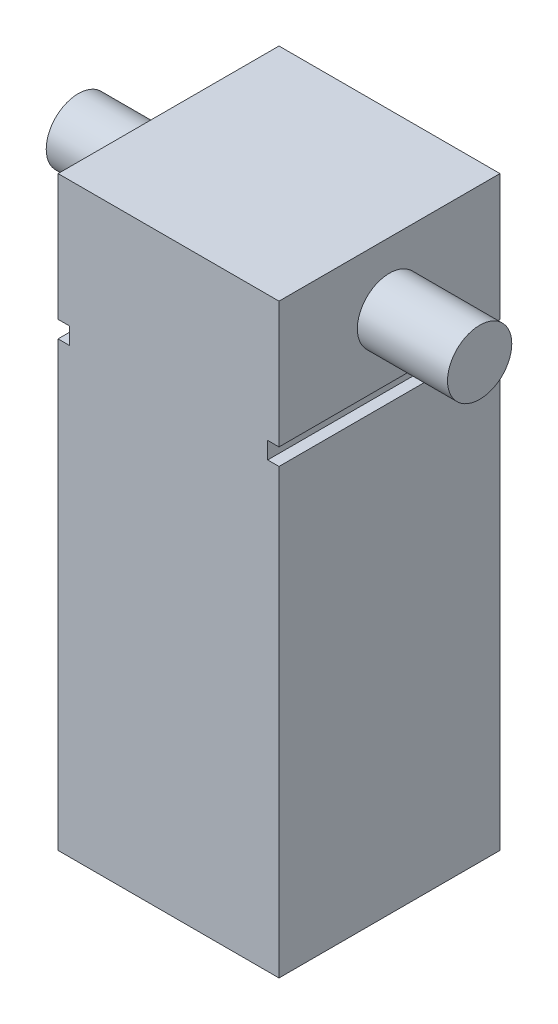
SolidWorks part; units mm, degrees
ref_plane "Front" through (0, 0, 0) normal (0, 0, 1) x (1, 0, 0)
ref_plane "Top" through (0, 0, 0) normal (0, 1, 0) x (1, 0, 0)
ref_plane "Right" through (0, 0, 0) normal (1, 0, 0) x (0, 0, -1)
sketch "Sketch1" plane through (0, 0, 0) normal (0, 0, 1) x (1, 0, 0)
  line L1 (-31.7522, 22.9478) -> (-6.8602, 22.9478)
  line L2 (-31.7522, 22.9478) -> (-31.7522, -43.0922)
  line L3 (-31.7522, -43.0922) -> (-6.8602, -43.0922)
  line L4 (-6.8602, 22.9478) -> (-6.8602, -43.0922)
  dimension "D1" = 66.04
  dimension "D2" = 24.892
extrude "Boss-Extrude1" add sketch "Sketch1" along normal blind 24.892
sketch "Sketch2" plane through (0, 0, 24.892) normal (0, 0, 1) x (1, 0, 0)
  line L1 (-31.7522, 22.9478) -> (-6.8602, 22.9478)
  line L2 (-31.7522, 22.9478) -> (-31.7522, 8.7238)
  line L3 (-31.7522, 8.7238) -> (-6.8602, 8.7238)
  line L4 (-31.7522, 22.9478) -> (-31.7522, -43.0922)
  line L5 (-31.7522, -43.0922) -> (-6.8602, -43.0922)
  line L6 (-6.8602, -43.0922) -> (-6.8602, 22.9478)
  line L7 (-6.8602, 22.9478) -> (-31.7522, 22.9478)
  line L8 (-31.7522, 22.9478) -> (-31.7522, -43.0922)
  line L9 (-31.7522, -43.0922) -> (-6.8602, -43.0922)
  line L10 (-6.8602, -43.0922) -> (-6.8602, 22.9478)
  line L11 (-6.8602, 22.9478) -> (-31.7522, 22.9478)
  line L12 (-6.8602, 22.9478) -> (-6.8602, 8.7238)
  line L13 (-31.7522, 8.7238) -> (-6.8602, 8.7238)
  line L14 (-31.7522, 8.7238) -> (-31.7522, 6.8188)
  line L15 (-31.7522, 6.8188) -> (-6.8602, 6.8188)
  line L16 (-6.8602, 8.7238) -> (-6.8602, 6.8188)
  line L17 (-31.7522, 8.7238) -> (-30.4822, 8.7238)
  line L18 (-31.7522, 8.7238) -> (-31.7522, 6.8188)
  line L19 (-31.7522, 6.8188) -> (-30.4822, 6.8188)
  line L20 (-30.4822, 8.7238) -> (-30.4822, 6.8188)
  line L21 (-6.8602, 8.7238) -> (-8.1302, 8.7238)
  line L22 (-6.8602, 8.7238) -> (-6.8602, 6.8188)
  line L23 (-6.8602, 6.8188) -> (-8.1302, 6.8188)
  line L24 (-8.1302, 8.7238) -> (-8.1302, 6.8188)
  line M10 (-31.7522, 22.9478) -> (-31.7522, -43.0922)
  dimension "D2" = 14.224
  dimension "D3" = 1.905
  dimension "D4" = 1.27
  dimension "D5" = 1.27
  dimension "D1" = 0
extrude "Cut-Extrude1" cut sketch "Sketch2" against normal up to surface (24.892 mm away) contours L20 L3 L15 M10 | L3 L24 L15 L10 region at (-31.1172, 7.7713, 24.892) region at (-7.4952, 7.7713, 24.892) up to face at (-19.3062, -10.0722, 0)
sketch "Sketch3" plane through (-31.7522, 0, 0) normal (-1, 0, 0) x (0, 0, 1)
  line L0 (12.446, 22.9478) -> (12.446, 15.8358)
  line L4 (0, 8.7238) -> (24.892, 8.7238)
  line L5 (24.892, 8.7238) -> (24.892, 22.9478)
  line L6 (24.892, 22.9478) -> (0, 22.9478)
  line L7 (0, 22.9478) -> (0, 8.7238)
  line L8 (0, 8.7238) -> (24.892, 8.7238)
  line L9 (24.892, 8.7238) -> (24.892, 22.9478)
  line L10 (24.892, 22.9478) -> (0, 22.9478)
  line L11 (0, 22.9478) -> (0, 8.7238)
  circle A0 centre (12.446, 15.8358) radius 3.6195
  dimension "D2" = 7.112
  dimension "D1" = 0
extrude "Boss-Extrude2" add sketch "Sketch3" along normal blind 10.16 contours A0 region at (-31.7522, 18.3227, 14.933)
sketch "Sketch4" plane through (-6.8602, 0, 0) normal (1, 0, 0) x (0, 0, -1)
  line L0 (-12.446, 22.9478) -> (-12.446, 15.8358)
  line L4 (-24.892, 8.7238) -> (0, 8.7238)
  line L5 (0, 8.7238) -> (0, 22.9478)
  line L6 (0, 22.9478) -> (-24.892, 22.9478)
  line L7 (-24.892, 22.9478) -> (-24.892, 8.7238)
  line L8 (-24.892, 8.7238) -> (0, 8.7238)
  line L9 (0, 8.7238) -> (0, 22.9478)
  line L10 (0, 22.9478) -> (-24.892, 22.9478)
  line L11 (-24.892, 22.9478) -> (-24.892, 8.7238)
  circle A0 centre (-12.446, 15.8358) radius 3.6195
  dimension "D2" = 7.112
  dimension "D1" = 0
extrude "Boss-Extrude3" add sketch "Sketch4" along normal blind 10.16 contours A0 region at (-6.8602, 18.3227, 9.959)
